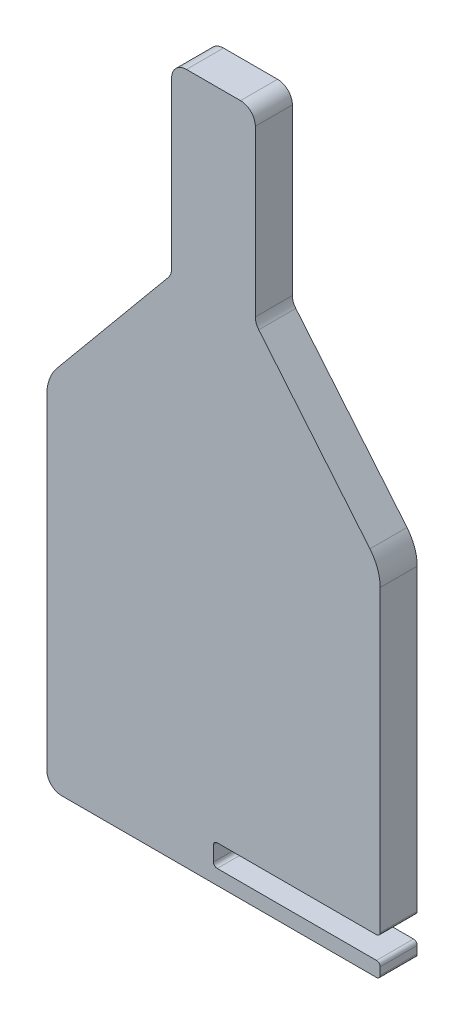
SolidWorks part; units mm, degrees
ref_plane "Alzado" through (0, 0, 0) normal (0, 0, 1) x (1, 0, 0)
ref_plane "Planta" through (0, 0, 0) normal (0, 1, 0) x (1, 0, 0)
ref_plane "Vista lateral" through (0, 0, 0) normal (1, 0, 0) x (0, 0, -1)
sketch "Croquis1" plane through (0, 0, 0) normal (0, 0, 1) x (1, 0, 0)
  line L0 (-5.65, 20) -> (-22.5, -0.3233)
  line L1 (-5.65, 45) -> (5.65, 45)
  line L2 (-22.5, -0.3233) -> (-22.5, -48.3233)
  line L3 (-22.5, -48.3233) -> (22.5, -48.3233)
  line L4 (22.5, -0.3233) -> (22.5, -48.3233)
  line L5 (-5.65, 45) -> (5.65, 45)
  line L6 (-5.65, 45) -> (-5.65, 20)
  line L8 (5.65, 45) -> (5.65, 19.9991)
  line L9 (5.65, 19.9991) -> (22.5, -0.3233)
  line L10 (0, 75.1867) -> (0, -77.6145) construction
  dimension "D1" = 45
  dimension "D2" = 25
  dimension "D3" = 5.65
  dimension "D4" = 22.5
  dimension "D5" = 45
  dimension "D6" = 5.65
  dimension "D7" = 26.3993
  dimension "D8" = 26.4
  dimension "D9" = 48
  dimension "D10" = 48
extrude "Saliente-Extruir1" add sketch "Croquis1" along normal blind 5 contours L6 L0 L2 L3 L4 L9 L8 L1
sketch "Croquis3" plane through (0, 0, 5) normal (0, 0, 1) x (1, 0, 0)
  line L0 (22.5, -0.3233) -> (22.5, -48.3233) construction
  line L1 (22.5, -43.3233) -> (0, -43.3233)
  line L2 (22.5, -43.3233) -> (22.5, -46.3233)
  line L3 (22.5, -46.3233) -> (0, -46.3233)
  line L4 (0, -43.3233) -> (0, -46.3233)
  line L5 (-22.5, -48.3233) -> (22.5, -48.3233) construction
  dimension "D1" = 3
  dimension "D2" = 2
  dimension "D3" = 22.5
extrude "Cortar-Extruir2" cut sketch "Croquis3" against normal up to surface (5 mm away) up to face at (0, 4.0882, 0)
fillet "Redondeo1" radius 2 5 edges at (-22.5, -48.3233, 2.5) (-5.65, 20, 2.5) (-5.65, 45, 2.5) (5.65, 19.9991, 2.5) (5.65, 45, 2.5)
fillet "Redondeo2" radius 6 2 edges at (-22.5, -0.3233, 2.5) (22.5, -0.3233, 2.5)
fillet "Redondeo3" radius 0.5 5 edges at (0, -43.3233, 2.5) (0, -46.3233, 2.5) (22.5, -48.3233, 2.5) (22.5, -46.3233, 2.5) (22.5, -43.3233, 2.5)
